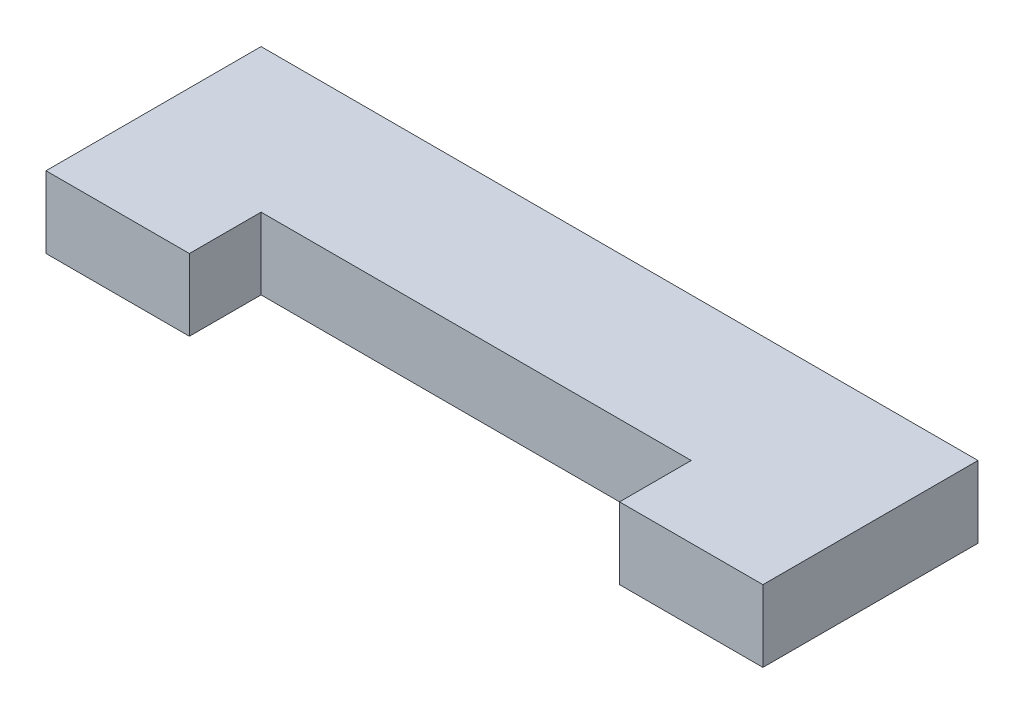
SolidWorks part; units mm, degrees
ref_plane "Front Plane" through (0, 0, 0) normal (0, 0, 1) x (1, 0, 0)
ref_plane "Top Plane" through (0, 0, 0) normal (0, 1, 0) x (1, 0, 0)
ref_plane "Right Plane" through (0, 0, 0) normal (1, 0, 0) x (0, 0, -1)
sketch "Sketch1" plane through (0, 0, 0) normal (0, 1, 0) x (1, 0, 0)
  line L0 (-20, -4) -> (-20, -8)
  line L1 (-12, -4) -> (12, -4)
  line L2 (-20, -4) -> (-20, 4)
  line L3 (-20, 4) -> (20, 4)
  line L4 (20, -4) -> (20, 4)
  line L5 (-20, -4) -> (20, 4) construction
  line L6 (-20, 4) -> (20, -4) construction
  line L7 (-20, -8) -> (-12, -8)
  line L8 (-12, -8) -> (-12, -4)
  line L9 (0, -55) -> (0, 55) construction
  line L10 (12, -8) -> (12, -4)
  line L11 (20, -8) -> (12, -8)
  line L12 (20, -4) -> (20, -8)
  line L13 (12, -4) -> (20, -4) construction
  line L14 (-20, -4) -> (-12, -4) construction
  point P0 (0, 0)
  dimension "D1" = 8
  dimension "D2" = 40
  dimension "D3" = 4
  dimension "D4" = 8
extrude "Boss-Extrude1" add sketch "Sketch1" along normal blind 4
equation "\"m3_hole\"= 3.5"
equation "\"m3_washer\"= 7.3"
equation "\"m3_nut\"= 5.3"
equation "\"plywood_thickness\" = 4.0"
equation "\"guide_width\"= 10.0"
equation "\"guide_length\"= 65.0"
equation "\"guide_tab_length\" = 10.0"
equation "\"guide_tab_width\" = 9.0"
equation "\"guide_thickness\" = 12.0"
equation "\"grinder_od\"= 52.0"
equation "\"grinder_id\"= 45.5"
equation "\"grinder_adjust_od\" = 58.0"
equation "\"funnel_width_from_adjust_ring\" = 13.0"
equation "\"drill_contact_diameter_small\" = 24.0"
equation "\"drill_contact_diameter_medium\" = 28.0"
equation "\"drill_contact_diameter_large\" = 39.0"
equation "\"drill_contact_diameter_tab\" = 31.0"
equation "\"drill_contact_ow_tab\" = 14.5"
equation "\"drill_contact_iw_tab\" = 8.7"
equation "\"drill_contact_small_height\" = 15.5"
equation "\"drill_contact_large_height\" = 34.5"
equation "\"plywood_peg_length\" = 40.0"
equation "\"plywood_peg_width\" = 8.0"
equation "\"D1@Sketch1\"=\"plywood_thickness\"*2"
equation "\"D2@Sketch1\"=\"plywood_peg_length\""
equation "\"D3@Sketch1\"=\"plywood_thickness\""
equation "\"D4@Sketch1\"=\"plywood_peg_width\""
equation "\"D1@Boss-Extrude1\"=\"plywood_thickness\""
